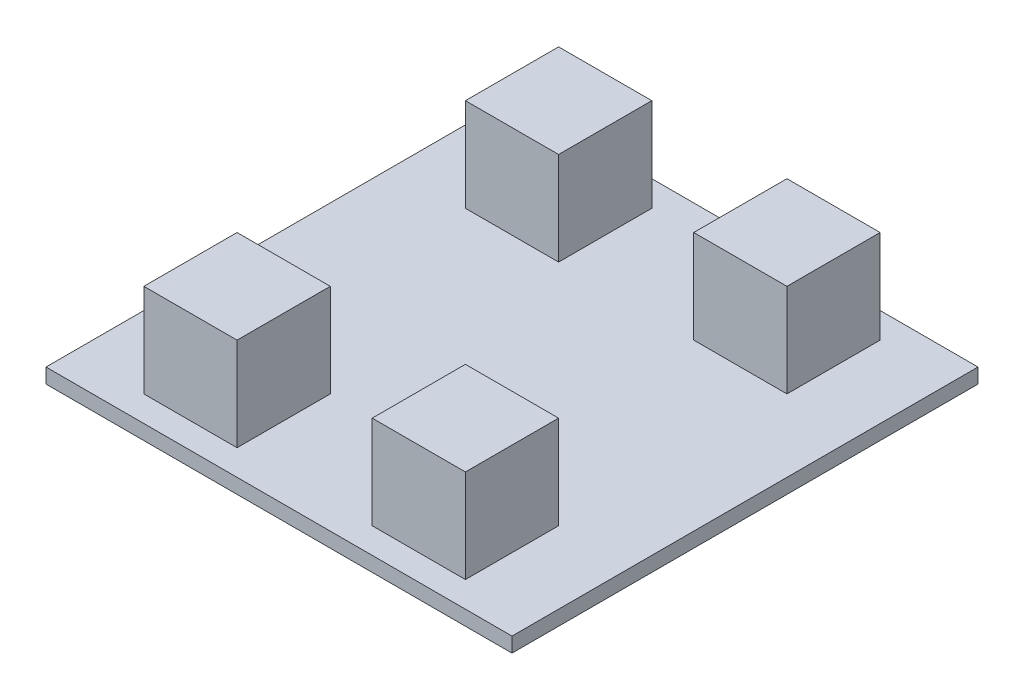
SolidWorks part; units mm, degrees
ref_plane "Front Plane" through (0, 0, 0) normal (0, 0, 1) x (1, 0, 0)
ref_plane "Top Plane" through (0, 0, 0) normal (0, 1, 0) x (1, 0, 0)
ref_plane "Right Plane" through (0, 0, 0) normal (1, 0, 0) x (0, 0, -1)
sketch "Sketch1" plane through (0, 0, 0) normal (0, 1, 0) x (1, 0, 0)
  line L1 (-50, -50) -> (50, -50)
  line L2 (-50, -50) -> (-50, 50)
  line L3 (-50, 50) -> (50, 50)
  line L4 (50, -50) -> (50, 50)
  line L5 (-50, -50) -> (50, 50) construction
  line L6 (-50, 50) -> (50, -50) construction
  point P0 (0, 0)
  dimension "D1" = 100
  dimension "D2" = 100
extrude "Boss-Extrude1" add sketch "Sketch1" along normal blind 3.175
sketch "Sketch2" plane through (0, 3.175, 0) normal (0, 1, 0) x (1, 0, 0)
  line L0 (-50, 50) -> (-50, -50) construction
  line L1 (-24.5, -24.5) -> (24.5, -24.5) construction
  line L2 (-24.5, -24.5) -> (-24.5, 24.5) construction
  line L3 (-24.5, 24.5) -> (24.5, 24.5) construction
  line L4 (24.5, -24.5) -> (24.5, 24.5) construction
  line L5 (-24.5, -24.5) -> (24.5, 24.5) construction
  line L6 (-24.5, 24.5) -> (24.5, -24.5) construction
  line L7 (-34.5, -24.5) -> (-14.5, -24.5)
  line L8 (-34.5, -24.5) -> (-34.5, -44.5)
  line L9 (-34.5, -44.5) -> (-14.5, -44.5)
  line L10 (-14.5, -24.5) -> (-14.5, -44.5)
  line L11 (-34.5, -24.5) -> (-14.5, -44.5) construction
  line L12 (-34.5, -44.5) -> (-14.5, -24.5) construction
  line L17 (14.5, -24.5) -> (34.5, -24.5)
  line L18 (14.5, -24.5) -> (14.5, -44.5)
  line L19 (14.5, -44.5) -> (34.5, -44.5)
  line L20 (34.5, -24.5) -> (34.5, -44.5)
  line L21 (14.5, -24.5) -> (34.5, -44.5) construction
  line L22 (14.5, -44.5) -> (34.5, -24.5) construction
  line L23 (-12.7462, 0) -> (12.7462, 0) construction
  line L24 (14.5, 44.5) -> (34.5, 44.5)
  line L25 (14.5, 24.5) -> (14.5, 44.5)
  line L26 (34.5, 24.5) -> (34.5, 44.5)
  line L27 (14.5, 24.5) -> (34.5, 24.5)
  line L28 (-34.5, 24.5) -> (-14.5, 24.5)
  line L29 (-14.5, 24.5) -> (-14.5, 44.5)
  line L30 (-34.5, 24.5) -> (-34.5, 44.5)
  line L31 (-34.5, 44.5) -> (-14.5, 44.5)
  circle A0 centre (0, 0) radius 40 construction
  point P0 (0, 0)
  point P8 (-24.5, -34.5)
  point P13 (-114.1176, -2.9477)
  point P14 (-94.6221, -27.7122)
  point P15 (0, 0)
  point P16 (-24.5, -37.9065)
  point P19 (24.5, -34.5)
  point P24 (0, 0)
  point P25 (24.5, -34.5)
  point P26 (24.5, 0)
  point P27 (0, 0)
  point P30 (24.5, 34.5)
  point P39 (-24.5, 34.5)
  dimension "D3" = 80
  dimension "D1" = 49
  dimension "D2" = 49
  dimension "D4" = 20
  dimension "D5" = 20
  dimension "D6" = 0
  dimension "D7" = 15.5
extrude "Boss-Extrude2" add sketch "Sketch2" along normal blind 20
